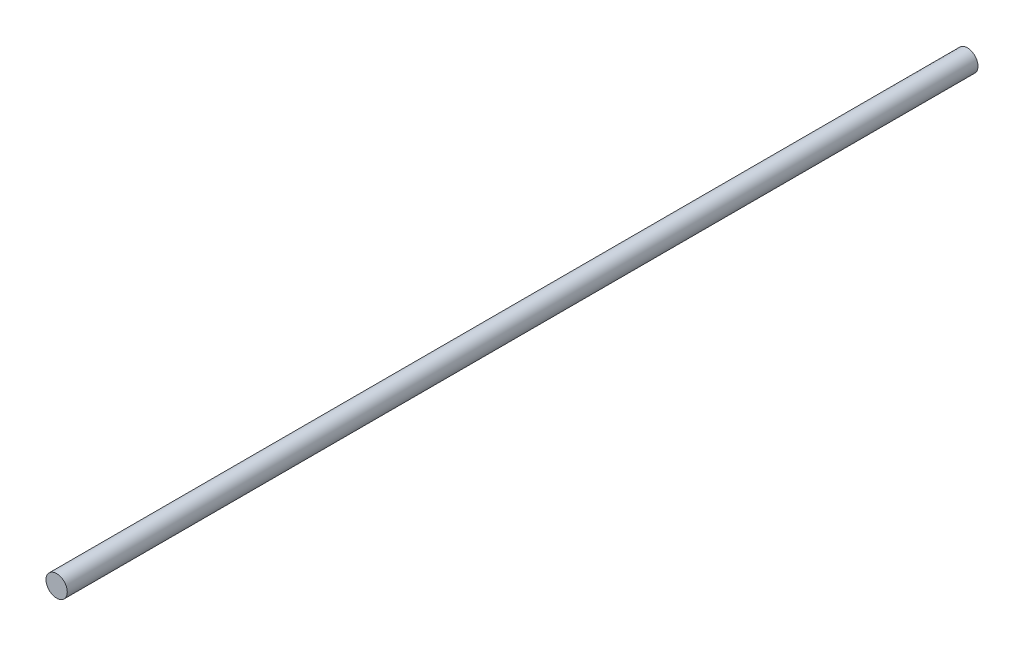
SolidWorks part; units mm, degrees
ref_plane "Plano frontal" through (0, 0, 0) normal (0, 0, 1) x (1, 0, 0)
ref_plane "Plano superior" through (0, 0, 0) normal (0, 1, 0) x (1, 0, 0)
ref_plane "Plano direito" through (0, 0, 0) normal (1, 0, 0) x (0, 0, -1)
sketch "Esboço1" plane through (0, 0, 0) normal (0, 0, 1) x (1, 0, 0)
  circle A0 centre (0, 0) radius 4
  dimension "D1" = 8
extrude "Ressalto-extrusão1" add sketch "Esboço1" along normal mid plane 342
ref_axis "Eixo1" through (0, 0, 171) along (0, 0, -1)
